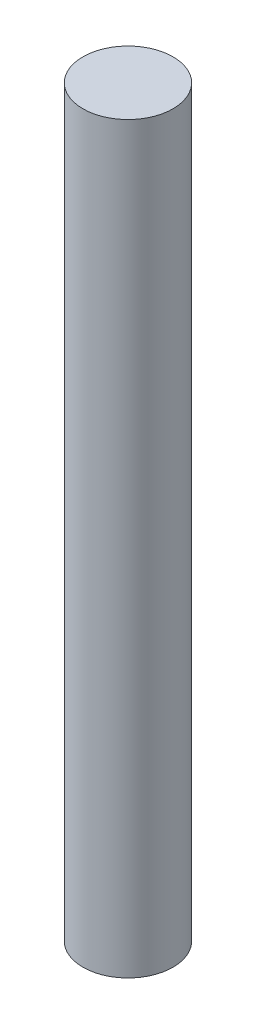
SolidWorks part; units mm, degrees
ref_plane "Спереди" through (0, 0, 0) normal (0, 0, 1) x (1, 0, 0)
ref_plane "Сверху" through (0, 0, 0) normal (0, 1, 0) x (1, 0, 0)
ref_plane "Справа" through (0, 0, 0) normal (1, 0, 0) x (0, 0, -1)
sketch "Эскиз1" plane through (0, 0, 0) normal (0, 1, 0) x (1, 0, 0)
  circle A0 centre (0, 0) radius 4
  dimension "D1" = 8
extrude "Бобышка-Вытянуть1" add sketch "Эскиз1" along normal blind 66
